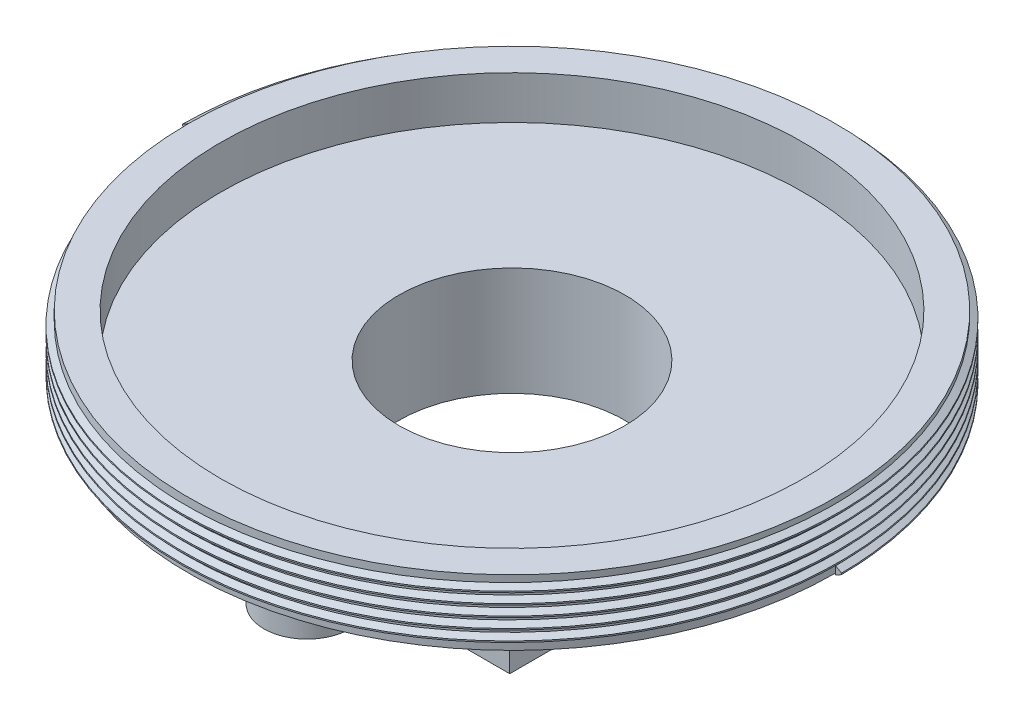
SolidWorks part; units mm, degrees
material "6061 Alloy"
ref_plane "Front Plane" through (0, 0, 0) normal (0, 0, 1) x (1, 0, 0)
ref_plane "Top Plane" through (0, 0, 0) normal (0, 1, 0) x (1, 0, 0)
ref_plane "Right Plane" through (0, 0, 0) normal (1, 0, 0) x (0, 0, -1)
sketch "Sketch1" plane through (0, 0, 0) normal (0, 1, 0) x (1, 0, 0)
  line L16 (-7.4938, 7.588) -> (-2, 7.588)
  line L33 (2, 9.488) -> (2, 7.588)
  line L34 (-2, 7.588) -> (-2, 9.488)
  line L35 (-1.9938, -7.612) -> (-7.4938, -7.612)
  line L36 (-2, -9.512) -> (-1.9938, -7.612)
  line L37 (2, -7.612) -> (2, -9.512)
  line L38 (7.5062, -7.612) -> (2, -7.612)
  line L39 (7.5062, 7.588) -> (7.5062, -7.612)
  line L40 (2, 7.588) -> (7.5062, 7.588)
  line L41 (-7.4938, -7.612) -> (-7.4938, 7.588)
  arc A4 (2, 9.488) -> (-2, 9.488) centre (0, 9.488) ccw
  arc A5 (-2, -9.512) -> (2, -9.512) centre (0, -9.512) ccw
  circle A6 centre (0, 9.488) radius 1.1
  circle A7 centre (0, -9.512) radius 1.1
  circle A8 centre (0, 0) radius 5.25
  circle A9 centre (0, 0) radius 13.519
  circle A10 centre (0, 0) radius 15.0225
  point P0 (0, 0)
  point P14 (0, 0)
  point P67 (0, 0)
  point P72 (0, 0)
  dimension "D5" = 2.2
  dimension "D11" = 10.5
  dimension "D4" = 27.038
  dimension "D6" = 30.045
  dimension "D2" = 15
  dimension "D3" = 15.2
  dimension "D8" = 2
  dimension "D10" = 1.9
  dimension "D17" = 5.5
  dimension "D18" = 4
  dimension "D19" = 19
extrude "Base" add sketch "Sketch1" against normal blind 4 contours L36 A5 L37 L38 L39 L40 L33 A4 L34 L16 L41 L35 A8 A6 A7 | A6 | A7 region at (-4.7469, 0, -7.3134) region at (0, 0, -9.488) region at (0, 0, 9.512)
extrude "Middle Holder" add sketch "Sketch1<3>" along normal blind 1.04 contours A9 A5 L36 L35 L41 L16 L34 A4 L33 L40 L39 L38 L37 | L36 A5 L37 L38 L39 L40 L33 A4 L34 L16 L41 L35 A8 A6 A7 | A7 | A6 region at (-4.7469, 0, -7.3134) region at (0, 0, -9.488) region at (0, 0, 9.512) region at (-13.1366, 0, 0)
sketch "Sketch1<3>" plane through (0, 0, 0) normal (0, 1, 0) x (1, 0, 0) same geometry as "Sketch1"
extrude "Outside Holder" add sketch "Sketch1<4>" along normal blind 3.04 contours A10 A9 region at (-14.5976, 0, 0)
sketch "Sketch1<4>" plane through (0, 0, 0) normal (0, 1, 0) x (1, 0, 0) same geometry as "Sketch1"
cosmetic thread "Cosmetic Thread1" parameters "D2"=29.045
thread "Thread1" pitch 0.5 method extrude profile "Thread Profile1" start angle 0, offset 0, length 2.75, pitch 0.5, diameter 30.045
ref_plane "Plane1" through (-15.0225, 3.04, 0) normal (0, 0, 1) x (-1, 0, 0)
sketch "Thread Profile1" plane through (-15.0225, 3.04, 0) normal (0, 0, 1) x (-1, 0, 0)
  line L0 (0, 0) -> (0, 0.5) construction
  line L1 (0, 0) -> (0.2706, 0.1562)
  line L2 (0.2706, 0.1562) -> (0.2706, 0.2187)
  line L3 (0.2706, 0.2187) -> (0, 0.375)
  line L4 (0.2706, 0.1875) -> (0, 0.1875) construction
  line L11 (0, 0) -> (0, 0.375)
  point P2 (0, 0)
  dimension "Pitch" = 0.5
  dimension "Profile_Angle" = 60
  dimension "Profile_Land" = 0.0625
  dimension "Profile_Height" = 0.2706
fillet "Fillet1" radius 1 1 edges at (-7.4938, 0, 0.012)
fillet "Fillet2" radius 1 1 edges at (7.5062, 0, 0.012)
hole_wizard "M2 Tapped Hole1" positions "Sketch5" profile "Sketch6" tap size "M2" standard "ISO"
sketch "Sketch5" plane through (0, -4, 0) normal (0, -1, 0) x (-1, 0, 0)
  point P0 (0, 9.488)
  point P3 (0, -9.512)
sketch "Sketch6" plane through (0, -4, -9.488) normal (1, 0, 0) x (0, 0, -1)
  line L0 (0, 0) -> (0, 4.4807)
  line L1 (0, 4.4807) -> (0.8, 4)
  line L2 (0.8, 4) -> (0.8, 0)
  line L5 (0.8, 0) -> (0, 0)
  line L10 (0, 4.4807) -> (-0.8, 4) construction
  line L11 (0, -6.35) -> (0, 107.95) construction
  dimension "Tap Drill Dia." = 1.6
  dimension "Tap Drill Depth" = 4
  dimension "Drill Angle" = 118
cosmetic thread "Hole Thread1" parameters "D1"=4, "D2"=2
cosmetic thread "Hole Thread2" parameters "D1"=4, "D2"=2
ref_plane "version number placement plane" through (-7.4938, 0, 0) normal (-1, 0, 0) x (0, 0, 1)
sketch "Sketch7" plane through (-7.4938, 0, 0) normal (-1, 0, 0) x (0, 0, 1)
  text T0 "v1.0" font "Century Gothic" height 2
extrude "Cut-Extrude1" cut sketch "Sketch7" against normal blind 1
